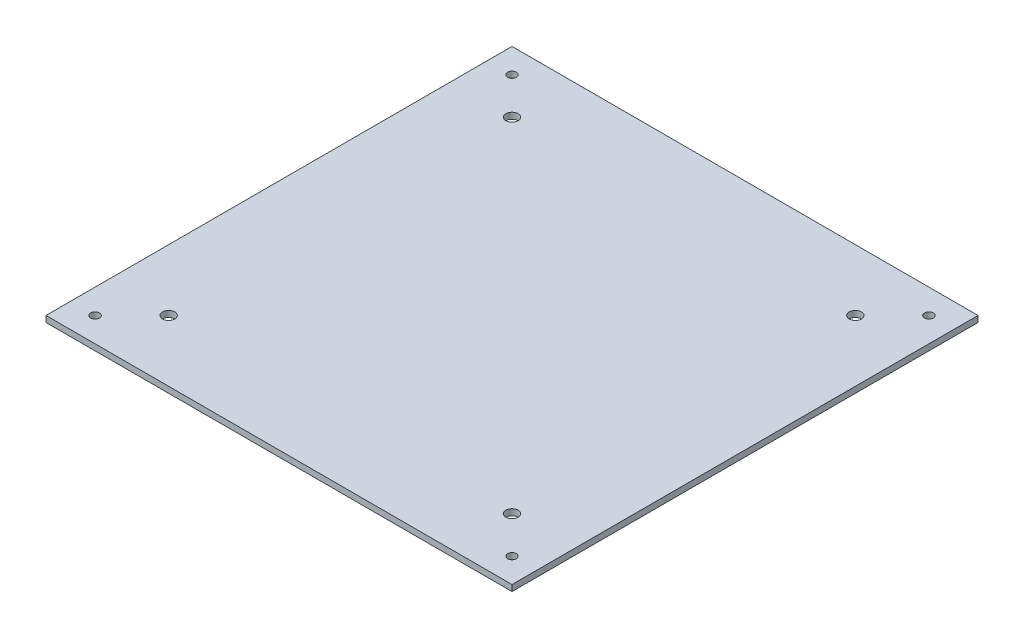
SolidWorks part; units mm, degrees
ref_plane "Front Plane" through (0, 0, 0) normal (0, 0, 1) x (1, 0, 0)
ref_plane "Top Plane" through (0, 0, 0) normal (0, 1, 0) x (1, 0, 0)
ref_plane "Right Plane" through (0, 0, 0) normal (1, 0, 0) x (0, 0, -1)
sketch "Sketch1" plane through (0, 0, 0) normal (0, 1, 0) x (1, 0, 0)
  line L1 (0, 0) -> (241.3, 0)
  line L2 (0, 0) -> (0, 241.3)
  line L3 (0, 241.3) -> (241.3, 241.3)
  line L4 (241.3, 0) -> (241.3, 241.3)
  dimension "9.5" = 241.3
  dimension "D2" = 241.3
extrude "Boss-Extrude1" add sketch "Sketch1" along normal blind 3.175
sketch "Sketch2" plane through (0, 3.175, 0) normal (0, 1, 0) x (1, 0, 0)
  line L0 (0, 0) -> (241.3, 0) construction
  line L1 (241.3, 0) -> (241.3, 241.3) construction
  line L2 (0, 0) -> (241.3, 241.3) construction
  circle A8 centre (209.55, 31.75) radius 3.175
  circle A9 centre (31.75, 31.75) radius 3.175
  circle A10 centre (31.75, 209.55) radius 3.175
  circle A11 centre (209.55, 209.55) radius 3.175
  circle A16 centre (228.6, 12.7) radius 2.286
  circle A17 centre (12.7, 12.7) radius 2.286
  circle A18 centre (12.7, 228.6) radius 2.286
  circle A19 centre (228.6, 228.6) radius 2.286
  point P10 (120.65, 120.65)
  dimension "D2" = 12.7
  dimension "D9" = 6.35
  dimension "D10" = 31.75
  dimension "D11" = 31.75
  dimension "D4" = 4.572
  dimension "D12" = 125.7236
  dimension "D13" = 177.8
  dimension "D3" = 12.7
  dimension "D5" = 4
  dimension "D7" = 215.9
  dimension "D8" = 152.6644
  dimension "D6" = 4
extrude "Cut-Extrude1" cut sketch "Sketch2" against normal through all
